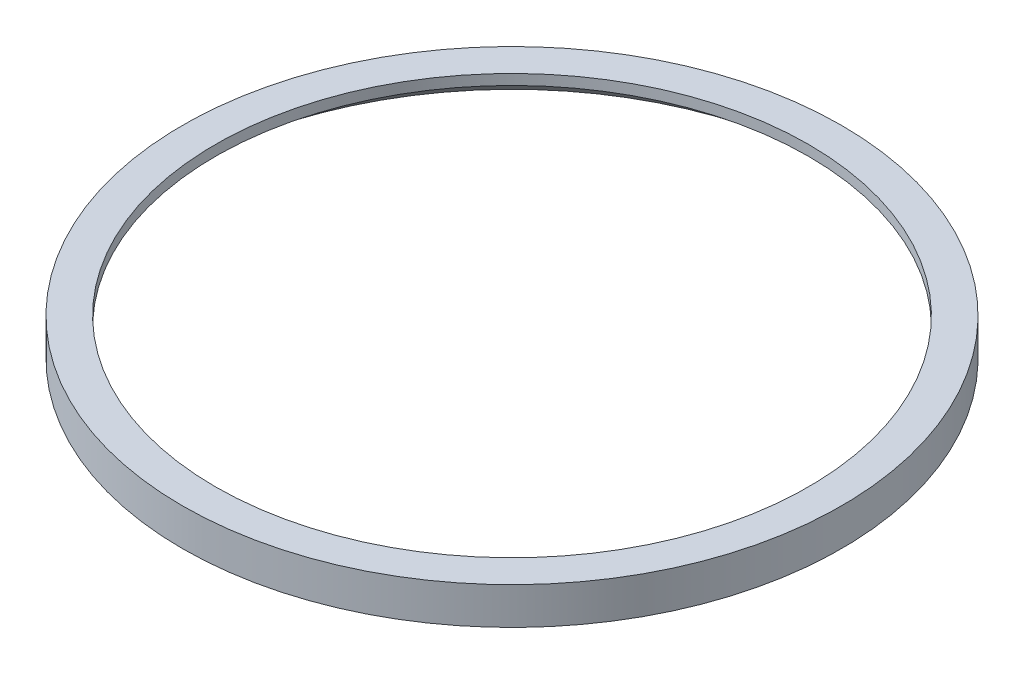
SolidWorks part; units mm, degrees
material "PVC Rigid"
ref_plane "Front" through (0, 0, 0) normal (0, 0, 1) x (1, 0, 0)
ref_plane "Top" through (0, 0, 0) normal (0, 1, 0) x (1, 0, 0)
ref_plane "Right" through (0, 0, 0) normal (1, 0, 0) x (0, 0, -1)
sketch "Sketch1" plane through (0, 0, 0) normal (0, 1, 0) x (1, 0, 0)
  circle A0 centre (0, 0) radius 40
  circle A1 centre (0, 0) radius 44.45
  dimension "D1" = 88.9
  dimension "D2" = 80
extrude "Boss-Extrude1" add sketch "Sketch1" along normal blind 5
sketch "Sketch2" plane through (0, 0, 0) normal (0, 0, 1) x (1, 0, 0)
  line L0 (0, 0) -> (40, 0) construction
  line L1 (40, 0) -> (40, 3.6)
  line L2 (40, 3.6) -> (44.45, 0)
  line L3 (44.45, 0) -> (40, 0)
  line L4 (0, 0) -> (0, 23.7803) construction
  point P4 (0, 0)
  point P10 (0, 0)
  point P11 (40, 3.6066)
  dimension "D1" = 3.6
revolve "Cut-Revolve1" cut sketch "Sketch2" angle 360 about L4
